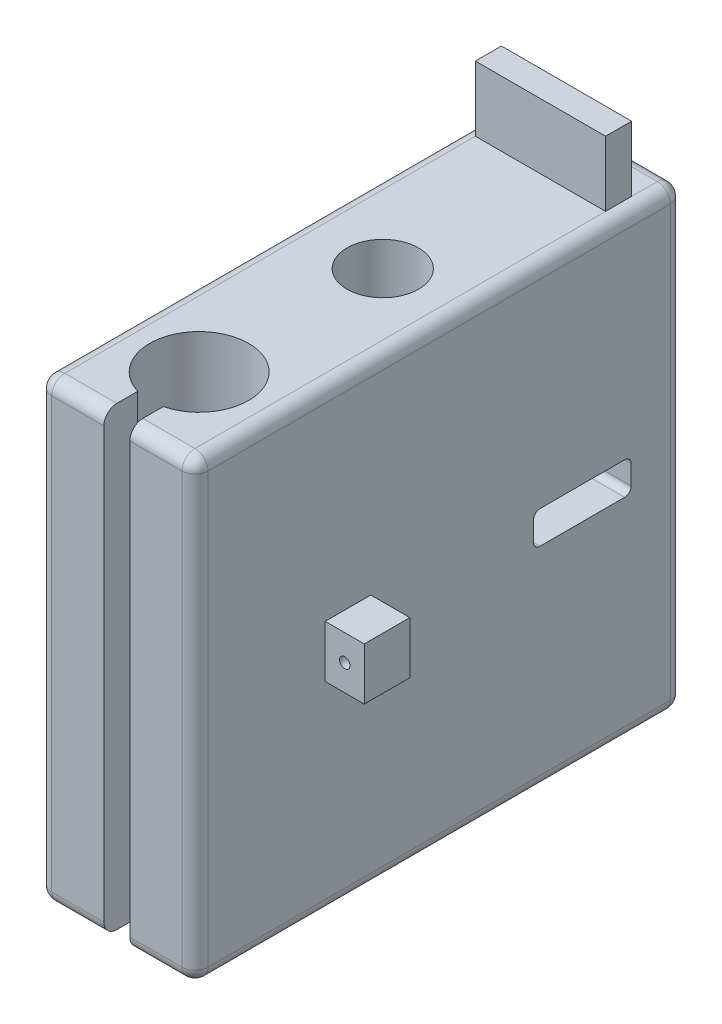
SolidWorks part; units mm, degrees
ref_plane "Front Plane" through (0, 0, 0) normal (0, 0, 1) x (1, 0, 0)
ref_plane "Top Plane" through (0, 0, 0) normal (0, 1, 0) x (1, 0, 0)
ref_plane "Right Plane" through (0, 0, 0) normal (1, 0, 0) x (0, 0, -1)
ref_plane "Plano1" through (-220, 0, 0) normal (1, 0, 0) x (0, 0, -1)
sketch "Esboço1" plane through (-220, 0, 0) normal (1, 0, 0) x (0, 0, -1)
  line L0 (-460.4999, 246.154) -> (-460.4999, 230.354) construction
  line L1 (-465.4999, 248.254) -> (-390.4999, 248.254)
  line L2 (-465.4999, 248.254) -> (-465.4999, 178.254)
  line L3 (-465.4999, 178.254) -> (-390.4999, 178.254)
  line L4 (-390.4999, 248.254) -> (-390.4999, 178.254)
  dimension "D1" = 75
  dimension "D2" = 70
  dimension "D3" = 5
extrude "Ressalto-extrusão1" add sketch "Esboço1" along normal blind 12 and the other way blind 12
sketch "Esboço3" plane through (0, 248.254, 0) normal (0, 1, 0) x (1, 0, 0)
  line L5 (-232, -465.4999) -> (-208, -465.4999) construction
  line L7 (-220, -465.4999) -> (-218, -465.4999)
  line L10 (-218, -465.4999) -> (-218, -460.3692)
  line L11 (-220, -465.4999) -> (-222, -465.4999)
  line L14 (-222, -465.4999) -> (-222, -460.292)
  arc A3 (-218, -460.3692) -> (-222, -460.292) centre (-219.8586, -452.9999) ccw
  circle A8 centre (-219.5085, -425.1499) radius 5.5
  circle A9 centre (-219.5085, -425.1499) radius 5.5
  dimension "D1" = 15.2
  dimension "D3" = 2
  dimension "D4" = 2
  dimension "D2" = 0.5
extrude "Corte-extrusão1" cut sketch "Esboço3" against normal through all
sketch "Esboço4" plane through (0, 0, 390.4999) normal (0, 0, -1) x (-1, 0, 0)
  line L0 (220, 248.254) -> (220, 178.254) construction
  line L1 (232, 248.254) -> (208, 248.254) construction
  line L2 (232, 178.254) -> (208, 178.254) construction
  circle A0 centre (219.8586, 238.254) radius 4.1
  circle A1 centre (219.8586, 188.254) radius 4.1
  dimension "D1" = 8.2
  dimension "D2" = 8.2
extrude "Corte-extrusão2" cut sketch "Esboço4" against normal blind 20
fillet "Filete1" radius 2 14 edges at (-227, 178.254, 465.4999) (-213, 178.254, 465.4999) (-213, 248.254, 465.4999) (-227, 248.254, 465.4999) (-208, 178.254, 427.9999) (-208, 248.254, 427.9999) (-208, 213.254, 465.4999) (-232, 178.254, 427.9999) (-232, 213.254, 465.4999) (-232, 248.254, 427.9999) (-220, 248.254, 390.4999) (-220, 178.254, 390.4999) (-208, 213.254, 390.4999) (-232, 213.254, 390.4999)
sketch "Esboço5" plane through (0, 0, 390.4999) normal (0, 0, -1) x (-1, 0, 0)
  line L8 (214.0294, 195.2585) -> (226.0294, 195.2486)
  line L9 (226.0294, 195.2486) -> (226.0589, 231.2486)
  line L10 (226.0589, 231.2486) -> (214.0589, 231.2584)
  line L11 (214.0589, 231.2584) -> (214.0294, 195.2585)
  line L12 (214.0294, 195.2585) -> (226.0294, 195.2486)
  line L13 (226.0294, 195.2486) -> (226.0589, 231.2486)
  line L14 (226.0589, 231.2486) -> (214.0589, 231.2584)
  line L15 (214.0589, 231.2584) -> (214.0294, 195.2585)
  dimension "D1" = 0
extrude "Corte-extrusão3" cut sketch "Esboço5" against normal blind 29
sketch "Esboço6" plane through (-232, 0, 0) normal (-1, 0, 0) x (0, 0, 1)
  line L0 (392.4999, 213.254) -> (463.4999, 213.254) construction
  line L1 (392.4999, 246.254) -> (392.4999, 180.254) construction
  line L2 (463.4999, 180.254) -> (463.4999, 246.254) construction
  line L3 (398.4999, 213.254) -> (413.4999, 213.254) construction
  line L4 (399.4999, 215.754) -> (412.4999, 215.754)
  line L5 (398.4999, 214.754) -> (398.4999, 211.754)
  line L6 (399.4999, 210.754) -> (412.4999, 210.754)
  line L7 (413.4999, 214.754) -> (413.4999, 211.754)
  arc A0 (412.4999, 215.754) -> (413.4999, 214.754) centre (412.4999, 214.754) cw
  arc A1 (412.4999, 210.754) -> (413.4999, 211.754) centre (412.4999, 211.754) ccw
  arc A2 (398.4999, 211.754) -> (399.4999, 210.754) centre (399.4999, 211.754) ccw
  arc A3 (399.4999, 215.754) -> (398.4999, 214.754) centre (399.4999, 214.754) ccw
  point P14 (413.4999, 215.754)
  point P17 (413.4999, 210.754)
  point P22 (398.4999, 215.754)
  dimension "D4" = 1
  dimension "D1" = 5
  dimension "D2" = 15
  dimension "D3" = 6
extrude "Corte-extrusão4" cut sketch "Esboço6" against normal blind 28
sketch "Esboço7" plane through (-208, 0, 0) normal (1, 0, 0) x (0, 0, -1)
  line L0 (-463.4999, 246.254) -> (-463.4999, 180.254) construction
  line L1 (-445.4999, 217.254) -> (-438.4999, 217.254)
  line L2 (-445.4999, 217.254) -> (-445.4999, 209.254)
  line L3 (-445.4999, 209.254) -> (-438.4999, 209.254)
  line L4 (-438.4999, 217.254) -> (-438.4999, 209.254)
  line L5 (-465.4999, 180.254) -> (-465.4999, 246.254) construction
  point P6 (-463.4999, 213.254)
  point P7 (-445.4999, 213.254)
  dimension "D1" = 7
  dimension "D2" = 8
  dimension "D3" = 20
extrude "Ressalto-extrusão2" add sketch "Esboço7" along normal blind 6 and the other way blind 30
ref_point "Ponto1"
sketch "Esboço9" plane through (0, 0, 445.4999) normal (0, 0, 1) x (1, 0, 0)
  line L0 (-205, 217.254) -> (-205, 209.254) construction
  line L3 (-208, 217.254) -> (-202, 217.254) construction
  line L6 (-208, 209.254) -> (-202, 209.254) construction
  line L7 (-208, 213.254) -> (-202, 213.254) construction
  line L8 (-208, 246.254) -> (-208, 180.254) construction
  line L9 (-202, 217.254) -> (-202, 209.254) construction
hole_wizard "Broca de rosquear para tarraxa de M2x0.41" positions "Esboço13" profile "Esboço14" hole size "M2x0.4" standard "Ansi Metric" end condition through all
sketch "Esboço13" plane through (0, 0, 445.4999) normal (0, 0, 1) x (1, 0, 0)
  line L0 (-205, 217.254) -> (-205, 209.254) construction
  point P0 (-205, 213.254)
sketch "Esboço14" plane through (-205, 213.254, 445.4999) normal (1, 0, 0) x (0, -1, 0)
  line L0 (0, 0) -> (0, 55)
  line L1 (0, 55) -> (0.8, 55)
  line L2 (0.8, 55) -> (0.8, 0)
  line L5 (0.8, 0) -> (0, 0)
  line L11 (0, -6.35) -> (0, 107.95) construction
  dimension "Thru Hole Dia." = 1.6
  dimension "Thru Hole Depth" = 55
sketch "Esboço15" plane through (0, 0, 445.4999) normal (0, 0, 1) x (1, 0, 0)
  line L0 (-235, 217.254) -> (-235, 209.254) construction
  line L1 (-238, 217.254) -> (-232, 217.254) construction
  line L2 (-238, 209.254) -> (-232, 209.254) construction
  line L3 (-238, 213.254) -> (-232, 213.254) construction
  line L4 (-238, 217.254) -> (-238, 209.254) construction
  line L5 (-232, 180.254) -> (-232, 246.254) construction
hole_wizard "Broca de rosquear para tarraxa de M2x0.42" positions "Esboço16" profile "Esboço17" hole size "M2x0.4" standard "Ansi Metric" end condition through all
sketch "Esboço16" plane through (0, 0, 445.4999) normal (0, 0, 1) x (1, 0, 0)
  line L0 (-235, 217.254) -> (-235, 209.254) construction
  point P0 (-235, 213.254)
sketch "Esboço17" plane through (-235, 213.254, 445.4999) normal (1, 0, 0) x (0, -1, 0)
  line L0 (0, 0) -> (0, 55)
  line L1 (0, 55) -> (0.8, 55)
  line L2 (0.8, 55) -> (0.8, 0)
  line L5 (0.8, 0) -> (0, 0)
  line L11 (0, -6.35) -> (0, 107.95) construction
  dimension "Thru Hole Dia." = 1.6
  dimension "Thru Hole Depth" = 55
sketch "Esboço18" plane through (0, 248.254, 0) normal (0, 1, 0) x (1, 0, 0)
  line L0 (-230, -392.4999) -> (-230, -463.4999) construction
  line L1 (-230, -396.4346) -> (-210, -396.4346)
  line L2 (-230, -396.4346) -> (-230, -400.4346)
  line L3 (-230, -400.4346) -> (-210, -400.4346)
  line L4 (-210, -396.4346) -> (-210, -400.4346)
  line L5 (-210, -463.4999) -> (-210, -392.4999) construction
  dimension "D1" = 4
extrude "Ressalto-extrusão3" add sketch "Esboço18" along normal blind 10
